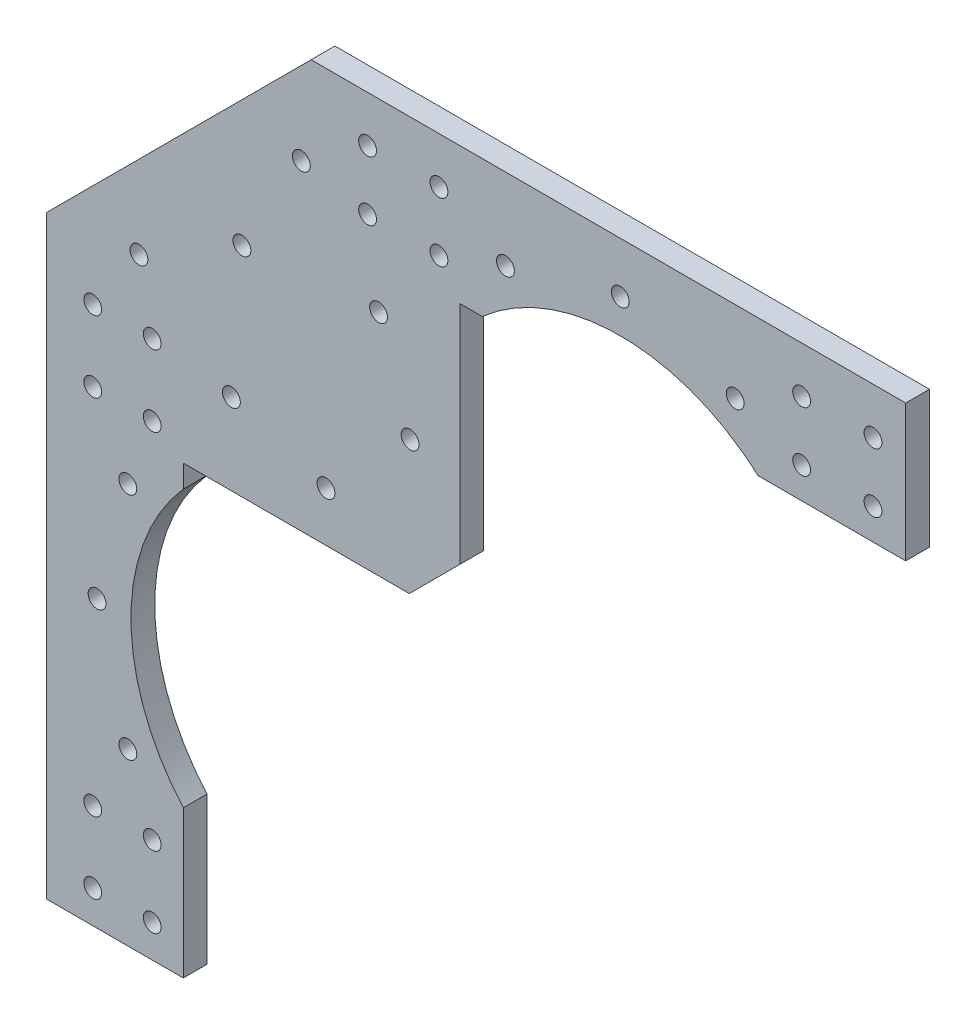
SolidWorks part; units mm, degrees
ref_plane "Front Plane" through (0, 0, 0) normal (0, 0, 1) x (1, 0, 0)
ref_plane "Top Plane" through (0, 0, 0) normal (0, 1, 0) x (1, 0, 0)
ref_plane "Right Plane" through (0, 0, 0) normal (1, 0, 0) x (0, 0, -1)
sketch "Sketch1" plane through (0, 0, 0) normal (0, 0, 1) x (1, 0, 0)
  line L0 (0, 0) -> (0, 73.5) construction
  line L1 (-96.5, -48) -> (-73.5, -48)
  line L2 (-96.5, -48) -> (-96.5, 52)
  line L4 (-73.5, -48) -> (-73.5, 27) construction
  line L5 (-52, 96.5) -> (48, 96.5)
  line L7 (-27, 73.5) -> (48, 73.5) construction
  line L8 (48, 96.5) -> (48, 73.5)
  line L9 (0, 0) -> (-73.5, 0) construction
  line L10 (-27, 73.5) -> (-73.5, 27) construction
  line L11 (-73.5, 73.5) -> (-27, 73.5) construction
  line L12 (-73.5, 27) -> (-73.5, 73.5) construction
  line L13 (-52, 96.5) -> (-96.5, 52)
  line L14 (-96.5, 96.5) -> (-52, 96.5) construction
  line L15 (-96.5, 52) -> (-96.5, 96.5) construction
  line L16 (-23.2069, 73.5) -> (-27, 73.5)
  line L17 (23.2069, 73.5) -> (48, 73.5)
  line L18 (-73.5, 27) -> (-73.5, 23.2069)
  line L19 (-73.5, -48) -> (-73.5, -23.2069)
  line L20 (-73.5, 23.2069) -> (-73.5, -23.2069) construction
  line L21 (-23.2069, 73.5) -> (23.2069, 73.5) construction
  line L22 (-73.5, 27) -> (-35.4853, 27)
  line L23 (-27, 35.4853) -> (-27, 73.5)
  line L24 (-35.4853, 27) -> (-27, 35.4853)
  arc A0 (23.2069, 73.5) -> (-23.2069, 73.5) centre (0, 47.3) ccw
  arc A1 (-73.5, 23.2069) -> (-73.5, -23.2069) centre (-47.3, 0) ccw
  dimension "D6" = 35
  dimension "D1" = 135
  dimension "D2" = 23
  dimension "D3" = 73.5
  dimension "D4" = 48
  dimension "D8" = 27
  dimension "D9" = 12
  dimension "D5" = 100
  dimension "D7" = 26.2
extrude "Boss-Extrude1" add sketch "Sketch1" along normal blind 4
ref_axis "Axis1" through (0, 0, -0.2) along (0, 0, 1)
sketch "Sketch3" plane through (0, 0, 4) normal (0, 0, 1) x (1, 0, 0)
  line L1 (30.5, 88.7259) -> (30.5, 78.7259) construction
  line L2 (30.5, 88.7259) -> (42.5, 88.7259) construction
  line L3 (42.5, 88.7259) -> (42.5, 78.7259) construction
  line L4 (30.5, 78.7259) -> (42.5, 78.7259) construction
  line L16 (-30.5, 78.7259) -> (0, 78.7259) construction
  line L17 (0, 78.7259) -> (0, 0) construction
  line L18 (0, 78.7259) -> (30.5, 78.7259) construction
  line L19 (-78.7259, 0) -> (0, 0) construction
  line L20 (-78.7259, -30.5) -> (-78.7259, 0) construction
  line L21 (-78.7259, 0) -> (-78.7259, 30.5) construction
  line L30 (-42.5, 88.7259) -> (-42.5, 78.7259) construction
  line L31 (-42.5, 88.7259) -> (-30.5, 88.7259) construction
  line L32 (-30.5, 88.7259) -> (-30.5, 78.7259) construction
  line L33 (-42.5, 78.7259) -> (-30.5, 78.7259) construction
  line L34 (-88.7259, 42.5) -> (-88.7259, 30.5) construction
  line L35 (-88.7259, 42.5) -> (-78.7259, 42.5) construction
  line L36 (-78.7259, 42.5) -> (-78.7259, 30.5) construction
  line L37 (-88.7259, 30.5) -> (-78.7259, 30.5) construction
  line L38 (-88.7259, -30.5) -> (-88.7259, -42.5) construction
  line L39 (-88.7259, -30.5) -> (-78.7259, -30.5) construction
  line L40 (-78.7259, -30.5) -> (-78.7259, -42.5) construction
  line L41 (-88.7259, -42.5) -> (-78.7259, -42.5) construction
  circle A0 centre (30.5, 78.7259) radius 1.5
  circle A1 centre (30.5, 88.7259) radius 1.5
  circle A2 centre (42.5, 88.7259) radius 1.5
  circle A3 centre (42.5, 78.7259) radius 1.5
  circle A24 centre (-42.5, 78.7259) radius 1.5
  circle A25 centre (-42.5, 88.7259) radius 1.5
  circle A26 centre (-30.5, 88.7259) radius 1.5
  circle A27 centre (-30.5, 78.7259) radius 1.5
  circle A28 centre (-88.7259, 30.5) radius 1.5
  circle A29 centre (-88.7259, 42.5) radius 1.5
  circle A30 centre (-78.7259, 42.5) radius 1.5
  circle A31 centre (-78.7259, 30.5) radius 1.5
  circle A32 centre (-88.7259, -42.5) radius 1.5
  circle A33 centre (-88.7259, -30.5) radius 1.5
  circle A34 centre (-78.7259, -30.5) radius 1.5
  circle A35 centre (-78.7259, -42.5) radius 1.5
  point P8 (30.5, 78.7259)
  point P12 (33.0196, 82.4917)
  point P15 (30.5, 78.7259)
  point P17 (36.7833, 83.4447)
  point P27 (0, 0)
  point P46 (0, 0)
  point P47 (0, 0)
  dimension "D1" = 3
  dimension "D8" = 30.5
  dimension "D2" = 12
  dimension "D6" = 10
  dimension "D3" = 78.7259
extrude "Cut-Extrude1" cut sketch "Sketch3" against normal blind 10
sketch "Sketch4" plane through (0, 0, 4) normal (0, 0, 1) x (1, 0, 0)
  line L0 (0, 0) -> (0, 88) construction
  line L1 (0, 0) -> (-63.6396, 63.6396) construction
  line L2 (0, 0) -> (-88, 0) construction
  line L3 (-82.8236, 19.3185) -> (-88, 0) construction
  line L4 (-88, 0) -> (-82.8236, -19.3185) construction
  line L5 (-80.9601, 53.6396) -> (-63.6396, 63.6396) construction
  line L6 (-63.6396, 63.6396) -> (-83.2677, 83.2677) construction
  line L7 (-19.3185, 82.8236) -> (0, 88) construction
  line L8 (-65.4074, 40.6586) -> (-40.6586, 65.4074) construction
  line L9 (-35.3553, 49.4975) -> (-49.4975, 35.3553) construction
  line L10 (-73.5, -48) -> (-73.5, -23.2069) construction
  line L11 (-35.4853, 27) -> (-27, 35.4853) construction
  circle A0 centre (-88, 0) radius 1.5
  circle A1 centre (-63.6396, 63.6396) radius 1.5
  circle A2 centre (0, 88) radius 1.5
  circle A3 centre (-80.9601, 53.6396) radius 1.5
  circle A4 centre (-53.6396, 80.9601) radius 1.5
  circle A5 centre (19.3185, 82.8236) radius 1.5
  circle A6 centre (-19.3185, 82.8236) radius 1.5
  circle A7 centre (-82.8236, 19.3185) radius 1.5
  circle A8 centre (-82.8236, -19.3185) radius 1.5
  circle A9 centre (-40.6586, 65.4074) radius 1.5
  circle A10 centre (-65.4074, 40.6586) radius 1.5
  circle A11 centre (-49.4975, 35.3553) radius 1.5
  circle A12 centre (-35.3553, 49.4975) radius 1.5
  dimension "D2" = 3
  dimension "D1" = 45
  dimension "D3" = 14.5
  dimension "D4" = 75
  dimension "D5" = 20
  dimension "D6" = 45.8162
  dimension "D7" = 75
  dimension "D8" = 75
  dimension "D9" = 35
  dimension "D10" = 20
  dimension "D11" = 15
  dimension "D12" = 15
extrude "Cut-Extrude2" cut sketch "Sketch4" against normal through all
equation "\"EyeDiameter\" = 35"
equation "\"BasePlaneDistance\" = \"EyeDiameter\"/2+19.84"
equation "\"EyeClearance\" = 2"
equation "\"L2Thickness\" = 8"
equation "\"L2_ID\" = 20"
equation "\"Offset\"= - 2"
equation "\"D3@Sketch1\"=\"BasePlaneDistance\" + 38.16 +\"Offset\""
equation "\"D3@Sketch3\"=\"BasePlaneDistance\" - 37.34+78.72592343"
equation "\"D7@Sketch1\"=24.20 - \"Offset\""
equation "\"D2@Sketch1\"=25.00 + \"Offset\""
